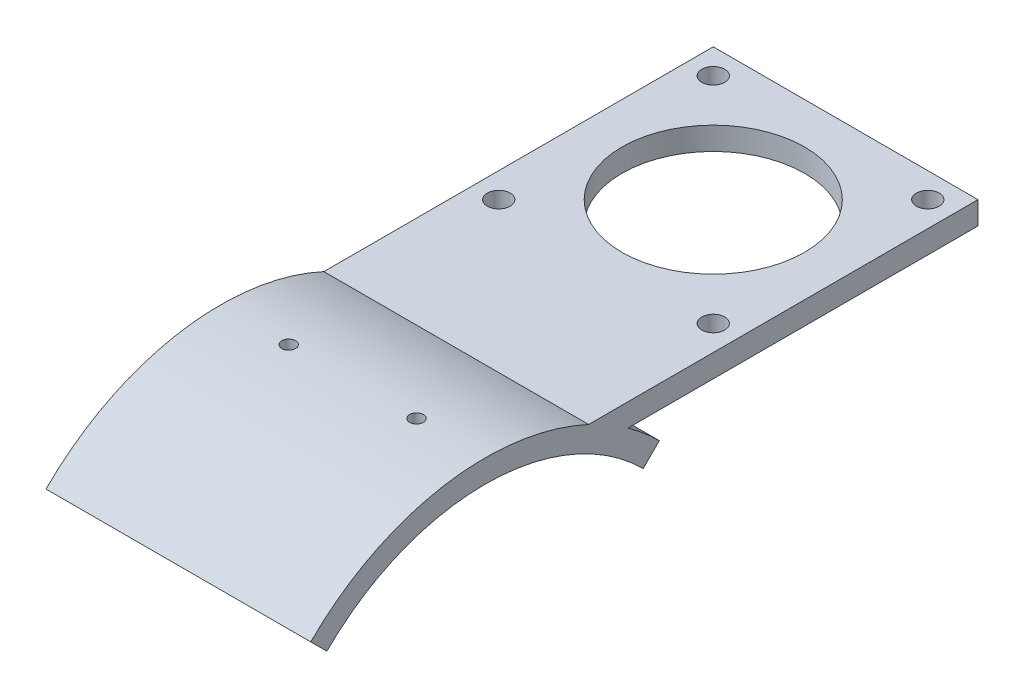
SolidWorks part; units mm, degrees
ref_plane "Front Plane" through (0, 0, 0) normal (0, 0, 1) x (1, 0, 0)
ref_plane "Top Plane" through (0, 0, 0) normal (0, 1, 0) x (1, 0, 0)
ref_plane "Right Plane" through (0, 0, 0) normal (1, 0, 0) x (0, 0, -1)
sketch "Sketch5" plane through (0, 0, 0) normal (1, 0, 0) x (0, 0, -1)
  line L0 (108, 0) -> (108, -5)
  line L1 (0, 0) -> (108, 0) construction
  line L2 (31.305, -5) -> (108, -5)
  line L3 (0, -5) -> (108, -5) construction
  line L4 (22.6936, 0) -> (108, 0)
  line L5 (34.6482, -14.3518) -> (38.1838, -10.8162)
  line L6 (-38.1838, -10.8162) -> (-34.6482, -14.3518)
  arc A0 (0, 0) -> (-34.6482, -14.3518) centre (0, -49) ccw
  arc A1 (0, 0) -> (34.6482, -14.3518) centre (0, -49) cw
  arc A2 (0, 5) -> (22.6936, 0) centre (0, -49) cw
  arc A3 (0, 5) -> (-38.1838, -10.8162) centre (0, -49) ccw
  arc A4 (31.305, -5) -> (38.1838, -10.8162) centre (0, -49) cw
  arc A5 (0, 5) -> (38.1838, -10.8162) centre (0, -49) cw construction
  dimension "D2" = 5
  dimension "D4" = 5
extrude "Boss-Extrude2" add sketch "Sketch5" along normal blind 58
sketch "Sketch6" plane through (0, 0, 0) normal (0, 1, 0) x (1, 0, 0)
  line L0 (0, 108) -> (5.5, 108) construction
  line L1 (58, 108) -> (0, 108) construction
  line L2 (5.5, 108) -> (5.5, 102.5) construction
  line L3 (29, 108) -> (29, 79) construction
  line L4 (29, 79) -> (58, 79) construction
  line L5 (58, 108) -> (58, 22.6936) construction
  circle A0 centre (5.5, 102.5) radius 2.5
  circle A1 centre (52.5, 102.5) radius 2.5
  circle A2 centre (52.5, 55.5) radius 2.5
  circle A3 centre (5.5, 55.5) radius 2.5
  circle A4 centre (29, 79) radius 20
  dimension "D4" = 5
  dimension "D5" = 40
  dimension "D1" = 5.5
  dimension "D2" = 5.5
  dimension "D3" = 29
extrude "Cut-Extrude3" cut sketch "Sketch6" against normal blind 58
sketch "Sketch7" plane through (0, 0, 0) normal (0, 1, 0) x (1, 0, 0)
  line L0 (29, 22.6936) -> (29, -38.1838) construction
  line L1 (58, 22.6936) -> (0, 22.6936) construction
  line L2 (58, -38.1838) -> (0, -38.1838) construction
  line L3 (0, 0) -> (15, 0) construction
  circle A0 centre (15, 0) radius 1.5
  circle A1 centre (43, 0) radius 1.5
  dimension "D2" = 3
  dimension "D1" = 15
extrude "Cut-Extrude4" cut sketch "Sketch7" against normal blind 58 and the other way blind 58
